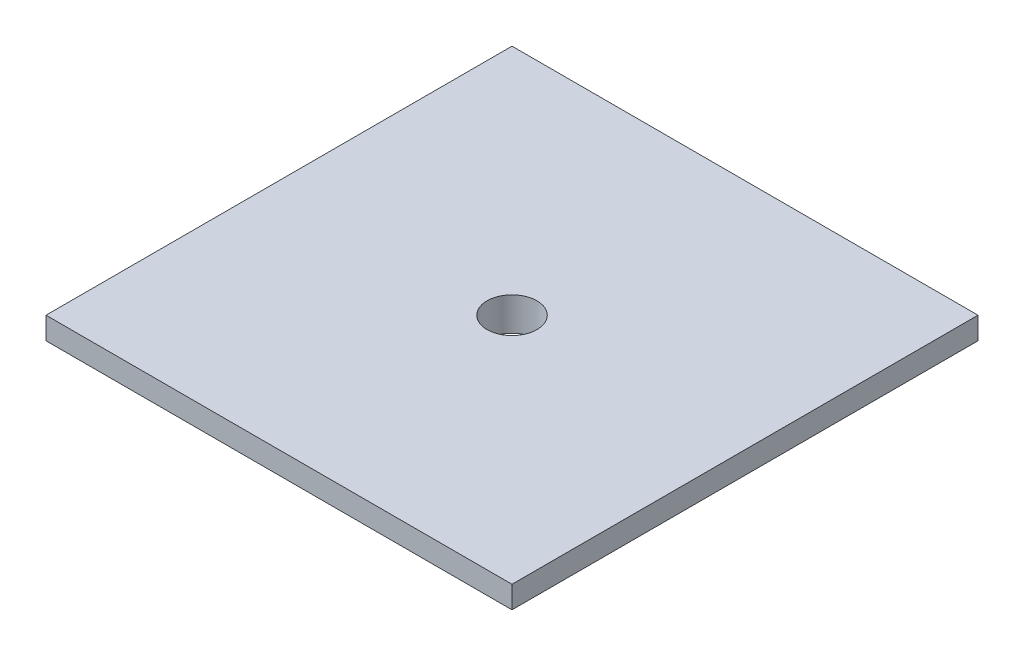
SolidWorks part; units mm, degrees
ref_plane "Front Plane" through (0, 0, 0) normal (0, 0, 1) x (1, 0, 0)
ref_plane "Top Plane" through (0, 0, 0) normal (0, 1, 0) x (1, 0, 0)
ref_plane "Right Plane" through (0, 0, 0) normal (1, 0, 0) x (0, 0, -1)
sketch "Sketch2" plane through (0, 0, 0) normal (0, 1, 0) x (1, 0, 0)
  line L1 (-105, -105) -> (105, -105)
  line L2 (-105, -105) -> (-105, 105)
  line L3 (-105, 105) -> (105, 105)
  line L4 (105, -105) -> (105, 105)
  line L5 (-105, -105) -> (105, 105) construction
  line L6 (-105, 105) -> (105, -105) construction
  point P0 (0, 0)
  dimension "D1" = 210
  dimension "D2" = 210
extrude "Boss-Extrude1" add sketch "Sketch2" along normal blind 10
sketch "Sketch3" plane through (0, 0, 0) normal (0, -1, 0) x (1, 0, 0)
  line L1 (-90, -90) -> (90, -90)
  line L2 (-90, -90) -> (-90, 90)
  line L3 (-90, 90) -> (90, 90)
  line L4 (90, -90) -> (90, 90)
  line L5 (-90, -90) -> (90, 90) construction
  line L6 (-90, 90) -> (90, -90) construction
  point P0 (0, 0)
  dimension "D1" = 180
  dimension "D2" = 180
extrude "Boss-Extrude2" add sketch "Sketch3" along normal blind 5
sketch "Sketch4" plane through (0, 10, 0) normal (0, 1, 0) x (1, 0, 0)
  circle A0 centre (0, 0) radius 11.25
  dimension "D1" = 22.5
extrude "Cut-Extrude1" cut sketch "Sketch4" against normal up to surface (15 mm away) up to face at (0, -5, 0)
